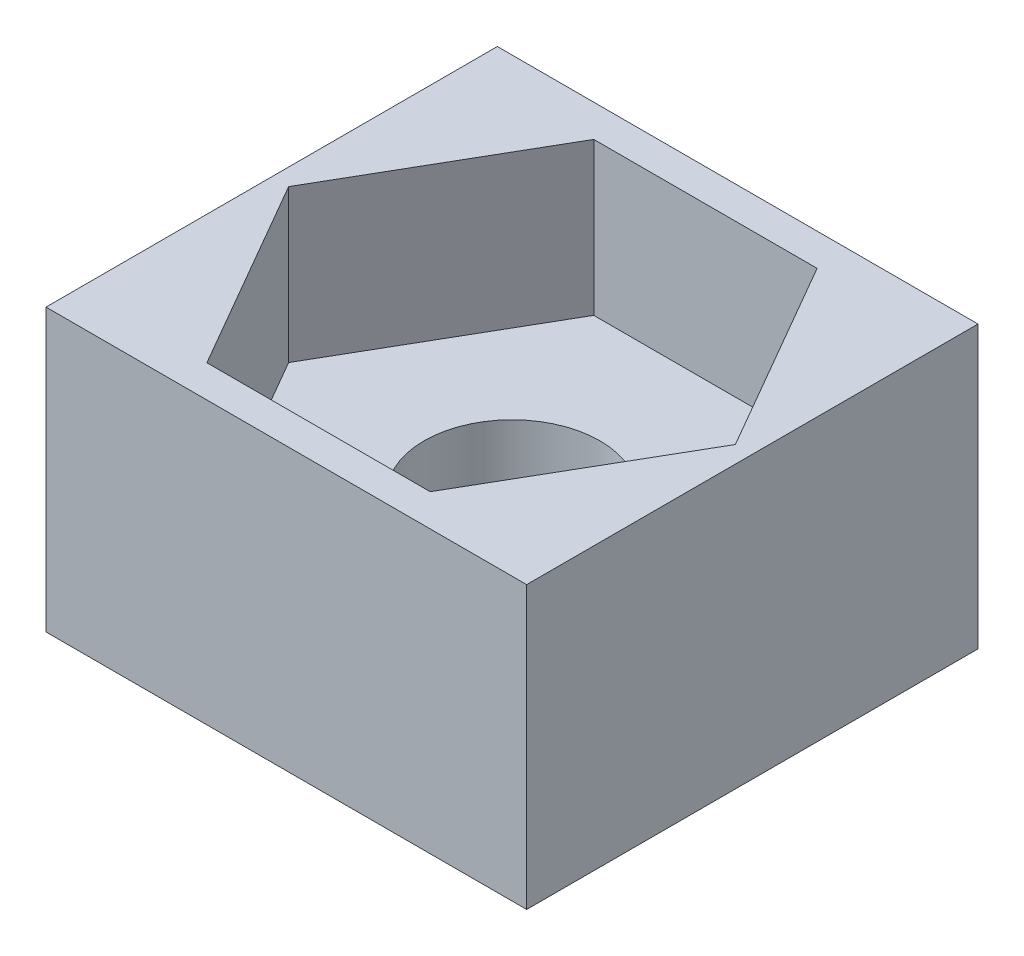
SolidWorks part; units mm, degrees
ref_plane "Plan de face" through (0, 0, 0) normal (0, 0, 1) x (1, 0, 0)
ref_plane "Plan de dessus" through (0, 0, 0) normal (0, 1, 0) x (1, 0, 0)
ref_plane "Plan de droite" through (0, 0, 0) normal (1, 0, 0) x (0, 0, -1)
sketch "Esquisse1" plane through (0, 0, 0) normal (0, 1, 0) x (1, 0, 0)
  line L0 (-3.8105, 0) -> (3.8105, 0) construction
  line L1 (3.8105, 0) -> (1.9053, 3.3)
  line L2 (1.9053, 3.3) -> (-1.9053, 3.3)
  line L3 (-1.9053, 3.3) -> (-3.8105, 0)
  line L4 (-3.8105, 0) -> (-1.9053, -3.3)
  line L5 (-1.9053, -3.3) -> (1.9053, -3.3)
  line L6 (1.9053, -3.3) -> (3.8105, 0)
  line L7 (-4.1, 3.85) -> (4.1, 3.85)
  line L8 (-4.1, 3.85) -> (-4.1, -3.85)
  line L9 (-4.1, -3.85) -> (4.1, -3.85)
  line L10 (4.1, 3.85) -> (4.1, -3.85)
  line L11 (-4.1, 3.85) -> (4.1, -3.85) construction
  line L12 (-4.1, -3.85) -> (4.1, 3.85) construction
  circle A0 centre (0, 0) radius 3.3 construction
  circle A1 centre (0, 0) radius 1.5
  dimension "D1" = 6.6
  dimension "D3" = 8.2
  dimension "D4" = 3
  dimension "D2" = 7.7
extrude "Boss.-Extru.1" add sketch "Esquisse1" along normal blind 4.8 contours L10 L7 L8 L9 L6 L5 L4 L3 L2 L1 region at (0, 0, -3.7375)
extrude "Boss.-Extru.2" add sketch "Esquisse1<3>" along normal blind 2.2 contours L5 L6 L1 L2 L3 L4 A1 region at (2.7706, 0, 1.5996)
sketch "Esquisse1<3>" plane through (0, 0, 0) normal (0, 1, 0) x (1, 0, 0) same geometry as "Esquisse1"
